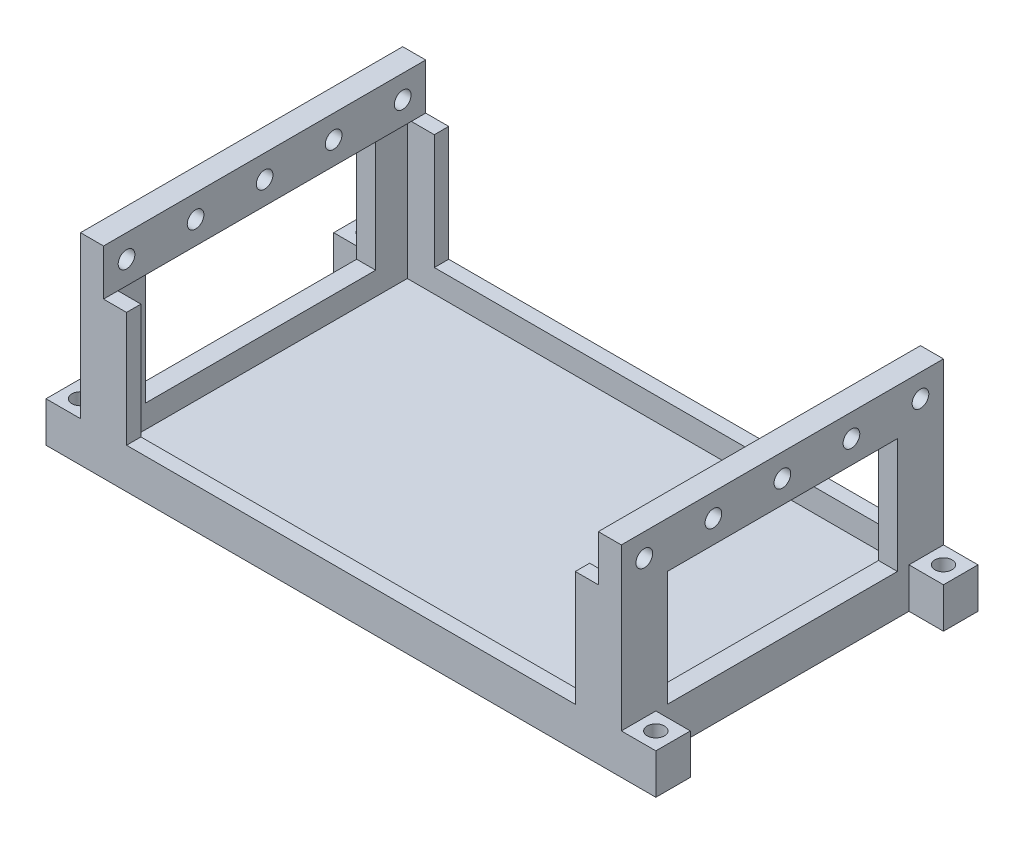
SolidWorks part; units mm, degrees
ref_plane "Front Plane" through (0, 0, 0) normal (0, 0, 1) x (1, 0, 0)
ref_plane "Top Plane" through (0, 0, 0) normal (0, 1, 0) x (1, 0, 0)
ref_plane "Right Plane" through (0, 0, 0) normal (1, 0, 0) x (0, 0, -1)
sketch "Sketch1" plane through (0, 0, 0) normal (0, 1, 0) x (1, 0, 0)
  line L0 (47, -944) -> (47, 49056) construction
  line L1 (0, 0) -> (94, 0)
  line L2 (0, 6) -> (0, 50)
  line L3 (0, 56) -> (94, 56)
  line L4 (94, 6) -> (94, 50)
  line L5 (0, 56) -> (-6, 56)
  line L7 (0, 50) -> (-6, 50)
  line L8 (-6, 56) -> (-6, 50)
  line L9 (-1000, 28) -> (49000, 28) construction
  line L10 (94, 50) -> (100, 50)
  line L11 (100, 56) -> (100, 50)
  line L12 (94, 56) -> (100, 56)
  line L14 (94, 0) -> (100, 0)
  line L15 (100, 0) -> (100, 6)
  line L16 (94, 6) -> (100, 6)
  line L18 (0, 6) -> (-6, 6)
  line L19 (-6, 0) -> (-6, 6)
  line L20 (0, 0) -> (-6, 0)
  circle A0 centre (-3, 53) radius 1.5
  circle A1 centre (97, 53) radius 1.5
  circle A2 centre (97, 3) radius 1.5
  circle A3 centre (-3, 3) radius 1.5
  point P11 (-3, 50)
  point P13 (-6, 53)
  point P17 (47, 56)
  point P18 (0, 28)
  dimension "D5" = 3
  dimension "D1" = 94
  dimension "D2" = 56
  dimension "D3" = 6
  dimension "D4" = 6
  dimension "D6" = 106
extrude "Boss-Extrude1" add sketch "Sketch1" along normal blind 3
sketch "Sketch2" plane through (0, 3, 0) normal (0, 1, 0) x (1, 0, 0)
  line L5 (3.3, 53.5) -> (90.7, 53.5)
  line L6 (3.3, 53.5) -> (3.3, 2.5)
  line L7 (3.3, 2.5) -> (90.7, 2.5)
  line L8 (0, 50) -> (0, 6)
  line L9 (-6, 0) -> (100, 0)
  line L10 (94, 6) -> (94, 50)
  line L11 (100, 56) -> (-6, 56)
  line L12 (0, 50) -> (0, 6)
  line L13 (-6, 0) -> (100, 0)
  line L14 (94, 6) -> (94, 50)
  line L15 (100, 56) -> (-6, 56)
  line L16 (90.7, 53.5) -> (90.7, 2.5)
  line L28 (100, 0) -> (100, 6)
  line L29 (100, 0) -> (100, 6)
  line L30 (100, 6) -> (94, 6)
  line L31 (100, 6) -> (94, 6)
  line L32 (94, 50) -> (100, 50)
  line L33 (94, 50) -> (100, 50)
  line L34 (100, 50) -> (100, 56)
  line L35 (100, 50) -> (100, 56)
  line L36 (-6, 56) -> (-6, 50)
  line L37 (-6, 56) -> (-6, 50)
  line L38 (-6, 50) -> (0, 50)
  line L39 (-6, 50) -> (0, 50)
  line L40 (0, 6) -> (-6, 6)
  line L41 (0, 6) -> (-6, 6)
  line L42 (-6, 6) -> (-6, 0)
  line L43 (-6, 6) -> (-6, 0)
  circle A0 centre (-3, 53) radius 1.5 construction
  circle A1 centre (-3, 53) radius 1.5
  circle A2 centre (97, 53) radius 1.5 construction
  circle A3 centre (97, 3) radius 1.5 construction
  circle A4 centre (-3, 3) radius 1.5 construction
  circle A5 centre (97, 53) radius 1.5
  circle A6 centre (97, 3) radius 1.5
  circle A7 centre (-3, 3) radius 1.5
  dimension "D2" = 2.5
  dimension "D3" = 3.3
  dimension "D4" = 3.3
  dimension "D5" = 2.5
  dimension "D1" = 0
extrude "Boss-Extrude2" add sketch "Sketch2" along normal blind 4
sketch "Sketch3" plane through (0, 7, 0) normal (0, 1, 0) x (1, 0, 0)
  line L0 (90.7, 53.5) -> (3.3, 53.5) construction
  line L1 (0, 56) -> (8, 56)
  line L2 (0, 56) -> (0, 53.5)
  line L3 (0, 53.5) -> (8, 53.5)
  line L4 (8, 56) -> (8, 53.5)
  line L5 (3.3, 53.5) -> (3.3, 2.5) construction
  line L6 (0, 53.5) -> (3.3, 53.5)
  line L7 (0, 53.5) -> (0, 48)
  line L8 (0, 48) -> (3.3, 48)
  line L9 (3.3, 53.5) -> (3.3, 48)
  line L10 (47, -946.5) -> (47, 49053.5) construction
  line L11 (100, 56) -> (-6, 56) construction
  line L12 (-996, 28) -> (49004, 28) construction
  line L13 (94, 48) -> (90.7, 48)
  line L14 (90.7, 53.5) -> (90.7, 48)
  line L15 (94, 53.5) -> (90.7, 53.5)
  line L16 (94, 53.5) -> (94, 48)
  line L17 (94, 53.5) -> (86, 53.5)
  line L18 (86, 56) -> (86, 53.5)
  line L19 (94, 56) -> (86, 56)
  line L20 (94, 56) -> (94, 53.5)
  line L21 (94, 2.5) -> (90.7, 2.5)
  line L22 (90.7, 2.5) -> (90.7, 8)
  line L23 (94, 8) -> (90.7, 8)
  line L24 (94, 2.5) -> (94, 8)
  line L25 (94, 0) -> (94, 2.5)
  line L26 (94, 0) -> (86, 0)
  line L27 (86, 0) -> (86, 2.5)
  line L28 (94, 2.5) -> (86, 2.5)
  line L29 (0, 8) -> (3.3, 8)
  line L30 (3.3, 2.5) -> (3.3, 8)
  line L31 (0, 2.5) -> (3.3, 2.5)
  line L32 (0, 2.5) -> (0, 8)
  line L33 (0, 2.5) -> (8, 2.5)
  line L34 (8, 0) -> (8, 2.5)
  line L35 (0, 0) -> (8, 0)
  line L36 (0, 0) -> (0, 2.5)
  line L37 (100, 56) -> (-6, 56) construction
  line L38 (0, 50) -> (0, 6) construction
  point P17 (47, 56)
  point P20 (3.3, 28)
  line M19 (100, 56) -> (-6, 56)
  line M20 (0, 50) -> (0, 6)
  line M21 (-6, 0) -> (100, 0)
  line M22 (94, 6) -> (94, 50)
  line M23 (90.7, 2.5) -> (3.3, 2.5)
  line M24 (3.3, 2.5) -> (3.3, 53.5)
  line M25 (3.3, 53.5) -> (90.7, 53.5)
  line M26 (90.7, 53.5) -> (90.7, 2.5)
  dimension "D1" = 8
  dimension "D2" = 8
extrude "Boss-Extrude3" add sketch "Sketch3" along normal blind 20 contours L8 L3 M20 M24 | L4 L3 M19 M20 M25 | L31 L29 M20 M24 | L34 L31 M21 M23 M20 | L23 L21 M22 M26 | L27 L21 M21 M22 M23 | L15 L13 M22 M26 | L18 L15 M19 M25 M22 region at (4, 7, -54.75) region at (1.65, 7, -50.75) region at (90, 7, -54.75) region at (92.35, 7, -50.75) region at (1.65, 7, -5.25) region at (4, 7, -1.25) region at (92.35, 7, -5.25) region at (90, 7, -1.25)
sketch "Sketch4" plane through (0, 27, 0) normal (0, 1, 0) x (1, 0, 0)
  line L0 (0, 0) -> (8, 0) construction
  line L1 (0, 56) -> (4, 56)
  line L2 (0, 56) -> (0, 0)
  line L3 (0, 0) -> (4, 0)
  line L4 (4, 56) -> (4, 0)
  line L5 (86, 0) -> (94, 0) construction
  line L6 (94, 56) -> (90, 56)
  line L7 (94, 56) -> (94, 0)
  line L8 (94, 0) -> (90, 0)
  line L9 (90, 56) -> (90, 0)
extrude "Boss-Extrude4" add sketch "Sketch4" along normal blind 8
sketch "Sketch5" plane through (0, 0, 0) normal (-1, 0, 0) x (0, 0, 1)
  line L0 (-48, 27) -> (-48, 35) construction
  line L2 (-56, 35) -> (0, 35) construction
  line L3 (-56, 35) -> (-56, 7) construction
  line L4 (0, 35) -> (0, 7) construction
  circle A0 centre (-52, 31) radius 1.45
  circle A1 centre (-40, 31) radius 1.45
  circle A2 centre (-28, 31) radius 1.45
  circle A3 centre (-16, 31) radius 1.45
  circle A4 centre (-4, 31) radius 1.45
  point P9 (-48, 31)
  dimension "D1" = 2.9
  dimension "D2" = 4
  dimension "D4" = 4
  dimension "D3" = 5
extrude "Cut-Extrude1" cut sketch "Sketch5" against normal through all
